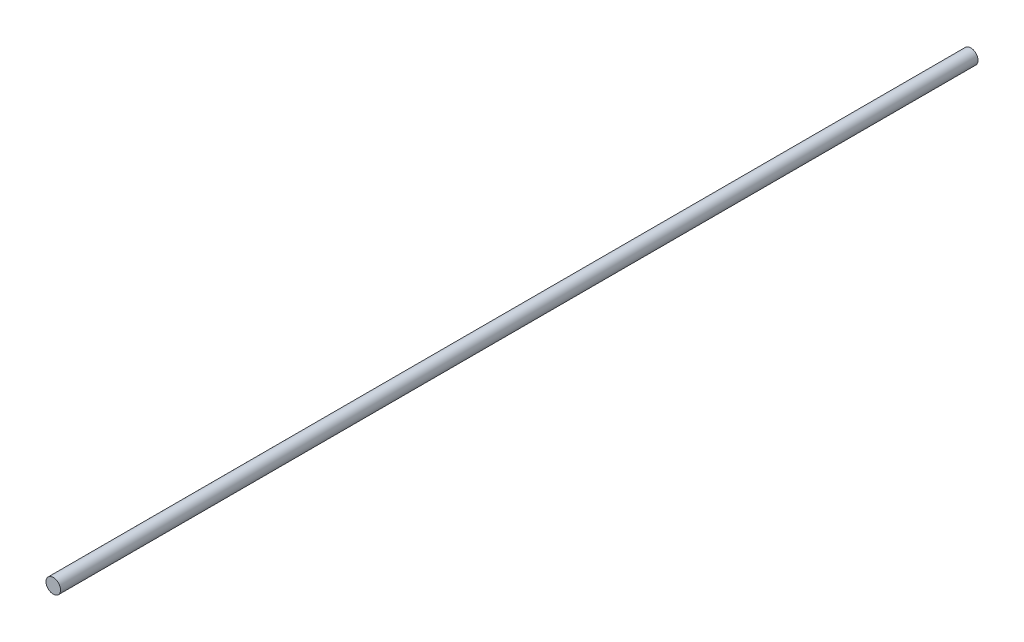
SolidWorks part; units mm, degrees
ref_plane "Front Plane" through (0, 0, 0) normal (0, 0, 1) x (1, 0, 0)
ref_plane "Top Plane" through (0, 0, 0) normal (0, 1, 0) x (1, 0, 0)
ref_plane "Right Plane" through (0, 0, 0) normal (1, 0, 0) x (0, 0, -1)
sketch3d "3DSketch2"
  circle A0 centre (0, 0, 0) radius 2.3813
  point P2 (0, 0, 2.3813)
ref_plane "Plane1" through (0, 0, 0) normal (0, 0, -1) x (-1, 0, 0)
extrude "Boss-Extrude1" add sketch "3DSketch2" along direction (0, 0, -1) on the side against the normal blind 300
